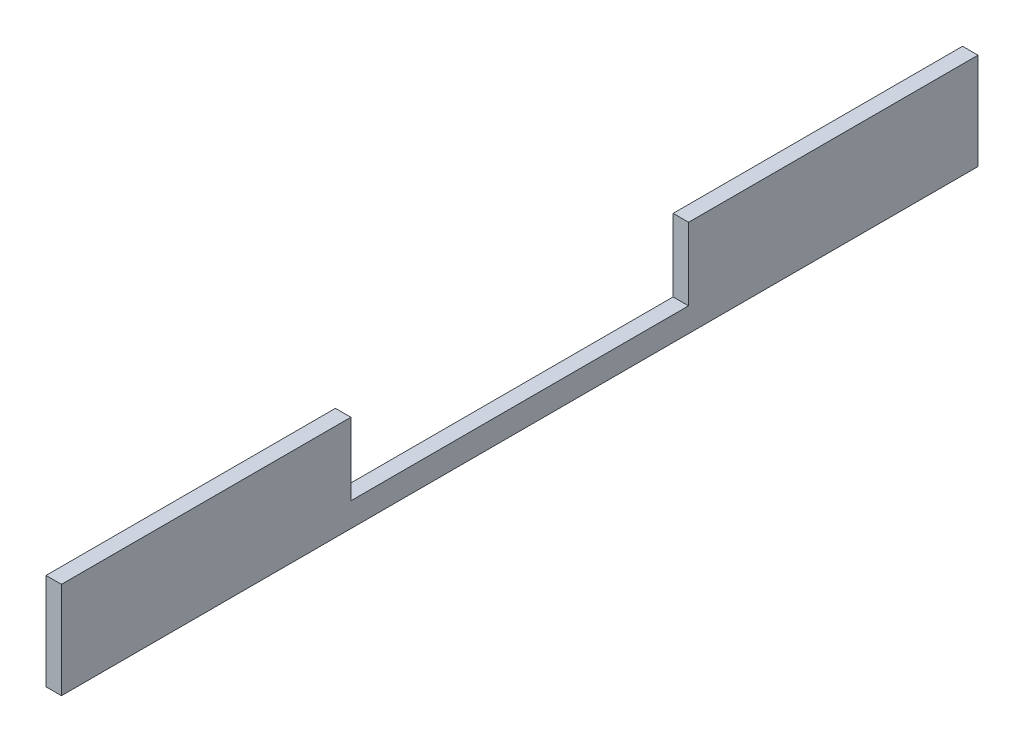
SolidWorks part; units mm, degrees
ref_plane "Front Plane" through (0, 0, 0) normal (0, 0, 1) x (1, 0, 0)
ref_plane "Top Plane" through (0, 0, 0) normal (0, 1, 0) x (1, 0, 0)
ref_plane "Right Plane" through (0, 0, 0) normal (1, 0, 0) x (0, 0, -1)
sketch "Sketch1" plane through (0, 0, 0) normal (1, 0, 0) x (0, 0, -1)
  line L1 (0, 0) -> (190, 0)
  line L2 (0, 0) -> (0, 20)
  line L3 (0, 20) -> (190, 20)
  line L4 (190, 0) -> (190, 20)
  dimension "D1" = 20
  dimension "D2" = 190
extrude "Boss-Extrude1" add sketch "Sketch1" along normal blind 3.2
sketch "Sketch2" plane through (0, 0, 0) normal (-1, 0, 0) x (0, 0, 1)
  line L0 (-95, 20) -> (-95, 5)
  line L3 (-190, 20) -> (0, 20) construction
  line L4 (-130, 20) -> (-130, 5)
  line L5 (-60, 20) -> (-60, 5)
  line L6 (-130, 5) -> (-60, 5)
  line L7 (-130, 20) -> (-60, 20)
  line M3 (0, 20) -> (-190, 20)
  dimension "D1" = 15
  dimension "D2" = 35
  dimension "D3" = 35
extrude "Cut-Extrude1" cut sketch "Sketch2" against normal blind 10 contours L4 L6 L0 M3 | L0 L6 L5 M3 region at (0, 12.5, -77.5) region at (0, 12.5, -112.5)
